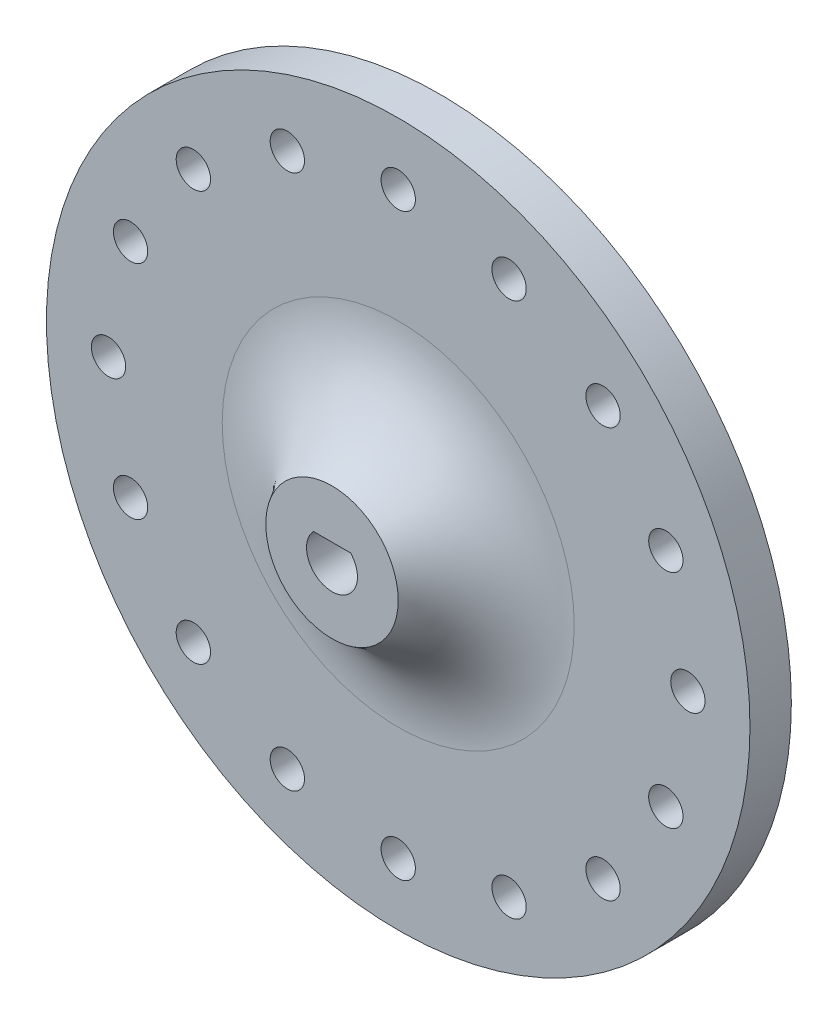
SolidWorks part; units mm, degrees
ref_plane "Plano frontal" through (0, 0, 0) normal (0, 0, 1) x (1, 0, 0)
ref_plane "Plano superior" through (0, 0, 0) normal (0, 1, 0) x (1, 0, 0)
ref_plane "Plano direito" through (0, 0, 0) normal (1, 0, 0) x (0, 0, -1)
sketch "Esboço1" plane through (0, 0, 0) normal (0, 0, 1) x (1, 0, 0)
  circle A0 centre (0, 0) radius 42.5
  dimension "D1" = 85
extrude "Ressalto-extrusão1" add sketch "Esboço1" along normal blind 5
sketch "Esboço2" plane through (0, 0, 5) normal (0, 0, 1) x (1, 0, 0)
  line L0 (-2.2462, 2.1) -> (2.2462, 2.1)
  line L1 (0, 0) -> (0, 2.1) construction
  arc A0 (-2.2462, 2.1) -> (2.2462, 2.1) centre (0, 0) ccw
  circle A1 centre (0, 0) radius 8
  dimension "D2" = 6.15
  dimension "D3" = 16
  dimension "D1" = 2.1
extrude "Ressalto-extrusão2" add sketch "Esboço2" along normal blind 8
fillet "Filete3" radius 15 1 edges at (8, 0, 5)
sketch "Esboço3" plane through (0, 0, 5) normal (0, 0, 1) x (1, 0, 0)
  line L0 (0, 0) -> (0, 35)
  circle A0 centre (0, 35) radius 2.075
  dimension "D1" = 4.15
  dimension "D2" = 35
extrude "Corte-extrusão1" cut sketch "Esboço3" against normal through all contours A0 region at (1.4257, 33.5743, 5)
pattern_circular "PadrãoCircular1" count 16 over 360 about axis through (0, 0, 5) along (0, 0, -1) of "Corte-extrusão1"
sketch "Esboço4" plane through (0, 0, 5) normal (0, 0, 1) x (1, 0, 0)
  line L1 (2.2462, 2.1) -> (-2.2462, 2.1)
  line L2 (2.2462, 2.1) -> (-2.2462, 2.1)
  arc A1 (-2.2462, 2.1) -> (2.2462, 2.1) centre (0, 0) ccw
  arc A2 (-2.2462, 2.1) -> (2.2462, 2.1) centre (0, 0) ccw
  dimension "D1" = 0
extrude "Corte-extrusão2" cut sketch "Esboço4" against normal through all
